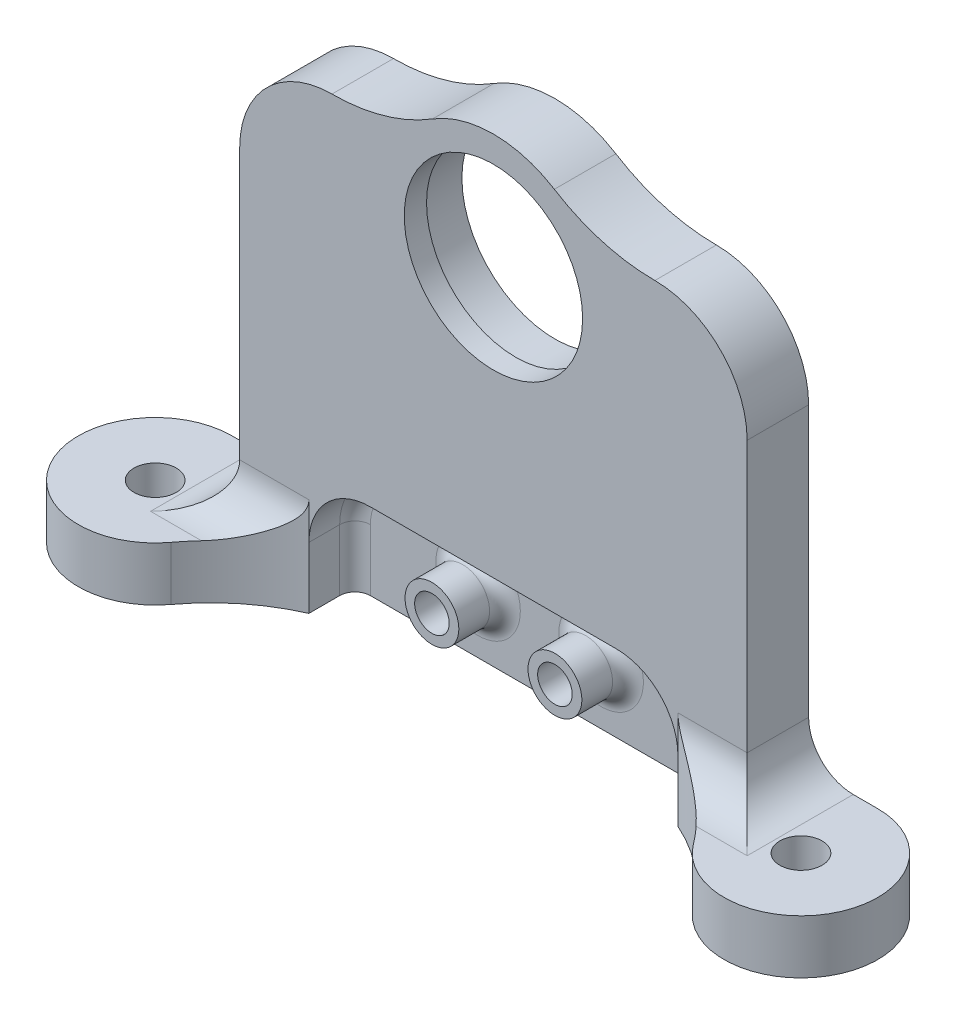
SolidWorks part; units mm, degrees
ref_plane "Front Plane" through (0, 0, 0) normal (0, 0, 1) x (1, 0, 0)
ref_plane "Top Plane" through (0, 0, 0) normal (0, 1, 0) x (1, 0, 0)
ref_plane "Right Plane" through (0, 0, 0) normal (1, 0, 0) x (0, 0, -1)
sketch "Sketch1" plane through (0, 0, 0) normal (0, 0, 1) x (1, 0, 0)
  line L1 (0, 15) -> (33, 15)
  line L2 (0, 15) -> (0, -51)
  line L3 (0, -51) -> (33, -51)
  line L4 (33, 15) -> (33, -51)
  point P5 (0, 0)
  dimension "D1" = 33
  dimension "D2" = 66
  dimension "D4" = 15
extrude "Boss-Extrude1" add sketch "Sketch1" along normal blind 8 separate body
sketch "Sketch3" plane through (0, 0, 8) normal (0, 0, 1) x (1, 0, 0)
  line L0 (0, 15) -> (0, -51) construction
  line L1 (33, 15) -> (0, 15) construction
  line L2 (9.5671, -23.097) -> (0, 0) construction
  line L3 (-17.5, 0) -> (-32.5, 0) construction
  line L4 (33, -51) -> (33, 15) construction
  line L5 (0, -51) -> (33, -51) construction
  circle A0 centre (25, -20) radius 2.75 construction
  circle A1 centre (0, 0) radius 11.6
  arc A2 (-17.5, 0) -> (6.697, -16.1679) centre (0, 0) ccw construction
  arc A3 (-32.5, 0) -> (12.4372, -30.0261) centre (0, 0) ccw construction
  arc A4 (12.4372, -30.0261) -> (6.697, -16.1679) centre (9.5671, -23.097) ccw construction
  dimension "D1" = 5.5
  dimension "D2" = 23.2
  dimension "D4" = 35
  dimension "D5" = 65
  dimension "D3" = 15
  dimension "D6" = 22.5
  dimension "D7" = 8
  dimension "D8" = 31
extrude "Cut-Extrude1" cut sketch "Sketch3" against normal through all
sketch "Sketch6" plane through (0, 0, 0) normal (0, 0, -1) x (-1, 0, 0)
  circle A0 centre (0, 0) radius 12.1
  dimension "D1" = 24.2
extrude "Cut-Extrude2" cut sketch "Sketch6" against normal blind 5.1
sketch "Sketch10" plane through (0, -51, 0) normal (0, -1, 0) x (1, 0, 0)
  line L0 (42, 0) -> (32, 0)
  line L1 (0, 0) -> (33, 0) construction
  line L2 (32, 10) -> (32, 0)
  line L3 (33, 8) -> (33, 0) construction
  arc A0 (42, 0) -> (32, 10) centre (42, 10) ccw
  circle A1 centre (42, 10) radius 2.75
  dimension "D1" = 5.5
  dimension "D2" = 20
  dimension "D3" = 1
extrude "Boss-Extrude4" add sketch "Sketch10" against normal blind 7
sketch "Sketch11" plane through (0, 0, 8) normal (0, 0, 1) x (1, 0, 0)
  line L1 (0, -51) -> (24, -51)
  line L2 (0, -51) -> (0, -35)
  line L3 (0, -35) -> (16, -35)
  line L4 (24, -51) -> (24, -43)
  arc A0 (16, -35) -> (24, -43) centre (16, -43) cw
  dimension "D1" = 8
  dimension "D2" = 16
  dimension "D3" = 24
extrude "Cut-Extrude3" cut sketch "Sketch11" against normal blind 6
sketch "Sketch12" plane through (0, 0, 2) normal (0, 0, 1) x (1, 0, 0)
  line L0 (8, -43) -> (0, -43) construction
  line L1 (0, -35) -> (0, -51) construction
  circle A0 centre (8, -43) radius 2.75
  dimension "D1" = 5.5
  dimension "D2" = 8
extrude "Cut-Extrude4" cut sketch "Sketch12" against normal blind 6
fillet "Fillet7" radius 2 3 edges at (24, -47, 2) (8, -35, 2) (21.6569, -37.3431, 2)
fillet "Fillet5" radius 25 1 edges at (32, -47.5, 8)
fillet "Fillet6" radius 5.8 2 edges at (33, -44, 4) (28.5, -44, 8)
sketch "Sketch13" plane through (0, 0, 0) normal (0, 0, -1) x (-1, 0, 0)
  circle A0 centre (-8, -43) radius 3.5
  circle A1 centre (-8, -43) radius 2.25
  dimension "D1" = 4.5
  dimension "D2" = 7
extrude "Boss-Extrude5" add sketch "Sketch13" against normal up to surface (8 mm away) up to face at (15.9174, -17.527, 8)
fillet "Fillet8" radius 2 1 edges at (4.5, -43, 2)
sketch "Sketch15" plane through (0, 0, 0) normal (0, 0, -1) x (-1, 0, 0)
  line L1 (-21, 9) -> (-21, -3) construction
  line L2 (0, 15) -> (-33, 15)
  line L3 (-33, 15) -> (-33, -3)
  line L4 (-21, -3) -> (-33, -3) construction
  arc A3 (-21, 9) -> (-33, -3) centre (-21, -3) ccw
  arc A4 (-21, 9) -> (-7.9245, 12.7358) centre (-21, 33.75) ccw
  arc A5 (0, 15) -> (-7.9245, 12.7358) centre (0, 0) ccw
  dimension "D1" = 15
  dimension "D2" = 12
  dimension "D3" = 18
extrude "Cut-Extrude5" cut sketch "Sketch15" against normal through all
mirror "Mirror1" about plane through (0, 15, 8) normal (1, 0, 0) of bodies 113 105
ref_plane "Mid Plane" through (0, 0, 0) normal (1, 0, 0) x (0, 0, -1)
